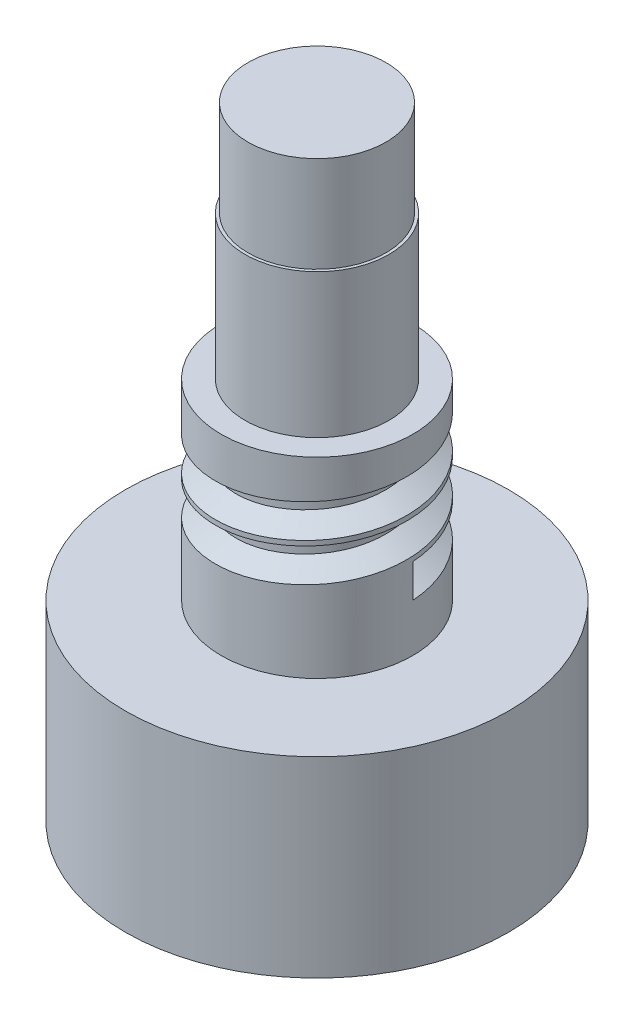
SolidWorks part; units mm, degrees
ref_plane "Front Plane" through (0, 0, 0) normal (0, 0, 1) x (1, 0, 0)
ref_plane "Top Plane" through (0, 0, 0) normal (0, 1, 0) x (1, 0, 0)
ref_plane "Right Plane" through (0, 0, 0) normal (1, 0, 0) x (0, 0, -1)
sketch "Sketch1" plane through (0, 0, 0) normal (0, 1, 0) x (1, 0, 0)
  circle A0 centre (0, 0) radius 2.286
  dimension "D1" = 4.572
extrude "Boss-Extrude1" add sketch "Sketch1" along normal blind 3.175
sketch "Sketch2" plane through (0, 0, 0) normal (0, -1, 0) x (-1, 0, 0)
  circle A0 centre (0, 0) radius 2.3825
  dimension "D1" = 4.765
extrude "Boss-Extrude2" add sketch "Sketch2" along normal blind 4.7622
sketch "Sketch3" plane through (0, -4.7622, 0) normal (0, -1, 0) x (-1, 0, 0)
  circle A0 centre (0, 0) radius 3.175
  dimension "D1" = 6.35
extrude "Boss-Extrude3" add sketch "Sketch3" along normal blind 3.175
sketch "Sketch4" plane through (0, -7.9372, 0) normal (0, -1, 0) x (-1, 0, 0)
  circle A0 centre (0, 0) radius 3.175
  dimension "D1" = 6.35
extrude "Boss-Extrude4" add sketch "Sketch4" along normal blind 3.175
thread "Thread2" pitch 1.27 method cut profile "Thread Profile3" start angle 0, offset 1.5875, length 3.175, pitch 1.27, diameter 6.35
ref_plane "Plane3" through (3.175, -9.5247, 0) normal (0, 0, 1) x (1, 0, 0)
sketch "Thread Profile3" plane through (3.175, -9.5247, 0) normal (0, 0, 1) x (1, 0, 0)
  line L0 (0, 0) -> (0, 1.27) construction
  line L11 (0, 0) -> (0, 1.1112)
  line L12 (0, 1.1112) -> (-0.6874, 0.7144)
  line L13 (-0.6874, 0.7144) -> (-0.6874, 0.3969)
  line L15 (-0.6874, 0.3969) -> (0, 0)
  line L17 (-0.6874, 0.5556) -> (0, 0.5556) construction
  point P2 (0, 0)
  dimension "Pitch" = 1.27
  dimension "Profile_Angle" = 60
  dimension "Profile_Land" = 0.3175
  dimension "Profile_Height" = 0.6874
sketch "Sketch11" plane through (0, -11.1122, 0) normal (0, -1, 0) x (-1, 0, 0)
  circle A0 centre (0, 0) radius 6.35
  dimension "D1" = 12.7
extrude "Boss-Extrude5" add sketch "Sketch11" along normal blind 6.35
